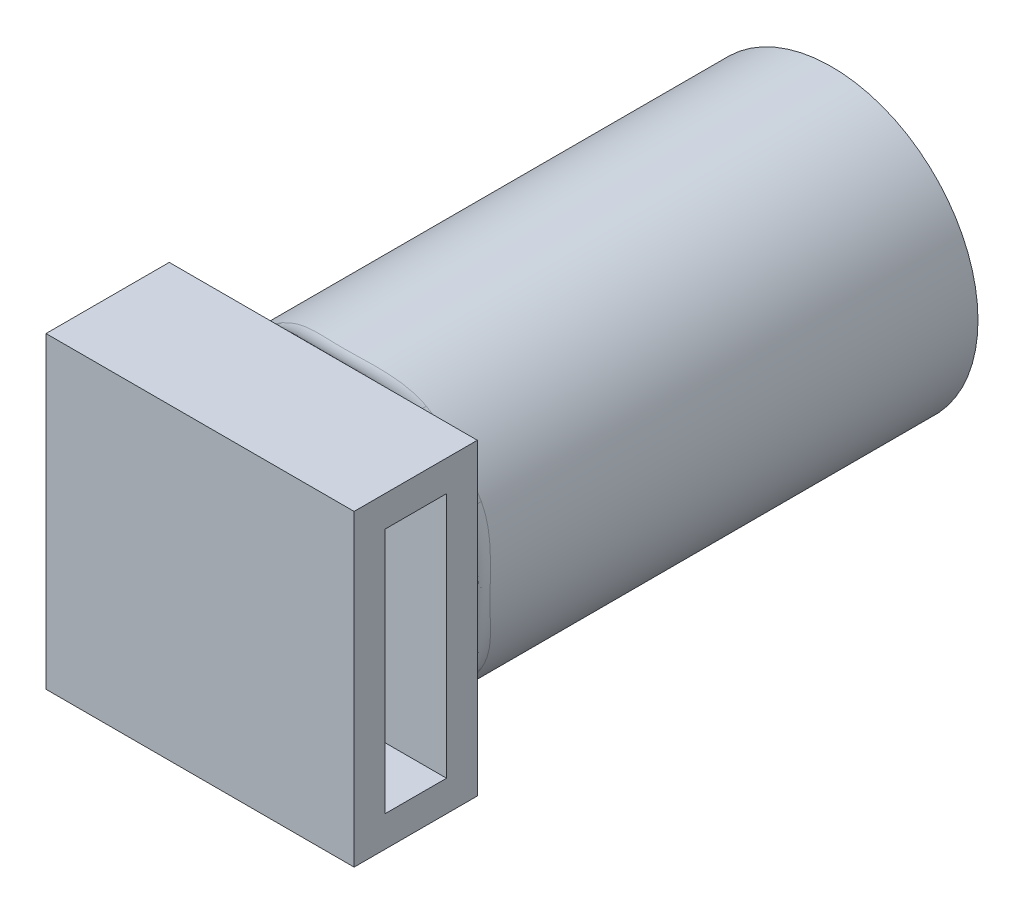
SolidWorks part; units mm, degrees
ref_plane "Front Plane" through (0, 0, 0) normal (0, 0, 1) x (1, 0, 0)
ref_plane "Top Plane" through (0, 0, 0) normal (0, 1, 0) x (1, 0, 0)
ref_plane "Right Plane" through (0, 0, 0) normal (1, 0, 0) x (0, 0, -1)
sketch "Sketch2" plane through (0, 0, 0) normal (0, 0, 1) x (1, 0, 0)
  circle A4 centre (0, 0) radius 4.75
  point P3 (25, 0)
  dimension "D1" = 9.5
ref_plane "Plane1" through (0, 0, 16.5) normal (0, 0, 1) x (1, 0, 0)
sketch "Sketch3" plane through (0, 0, 16.5) normal (0, 0, 1) x (1, 0, 0)
  line L0 (-5, 5) -> (5, 5)
  line L1 (-5, 5) -> (-5, -5)
  line L2 (-5, -5) -> (5, -5)
  line L3 (5, 5) -> (5, -5)
  circle A0 centre (0, 0) radius 4.75
  point P3 (0, 5)
  point P9 (5, 0)
  dimension "D1" = 9.5
  dimension "D2" = 10
loft "Loft1" add profiles "Sketch2", "Sketch3" connector at (0.4143, 4.7319, 0) connector at (0.1582, 4.7474, 16.5)
sketch "Sketch4" plane through (0, 0, 0) normal (0, 1, 0) x (1, 0, 0)
  line L1 (1, -12) -> (-1, -12)
  line L2 (1, -12) -> (1, -7)
  line L3 (1, -7) -> (-1, -7)
  line L4 (-1, -12) -> (-1, -7)
  line L7 (-4.75, 0) -> (-4.75, -16.5) construction
  line L8 (4.75, 0) -> (-4.75, 0) construction
  dimension "D1" = 7
  dimension "D2" = 3.75
  dimension "D3" = 5
  dimension "D4" = 2
extrude "Boss-Extrude4" add sketch "Sketch3<7>" along normal blind 4 contours A0 L3 L0 L1 | A0 L1 L2 L3 | A0 | A0 L0 L1 | A0 L2 L3 region at (0, 4.8586, 16.5) region at (0, 0, 16.5)
sketch "Sketch3<7>" plane through (0, 0, 16.5) normal (0, 0, 1) x (1, 0, 0) same geometry as "Sketch3"
sketch "Sketch8" plane through (5, 0, 0) normal (1, 0, 0) x (0, 0, -1)
  line L0 (-20.5, 5) -> (-20.5, -5) construction
  line L1 (-19.5, 4) -> (-17.5, 4)
  line L2 (-19.5, 4) -> (-19.5, -4)
  line L3 (-19.5, -4) -> (-17.5, -4)
  line L4 (-17.5, 4) -> (-17.5, -4)
  line L5 (-20.5, 5) -> (-16.5, 5) construction
  point P4 (-19.5, 0)
  point P7 (-20.5, 0)
  point P8 (-18.5, 4)
  point P11 (-18.5, 5)
  dimension "D1" = 2
  dimension "D2" = 8
extrude "Cut-Extrude2" cut sketch "Sketch8" against normal through all both and the other way through all
fillet "Fillet1" radius 1 1 edges at (4.75, 0, 16.5)
